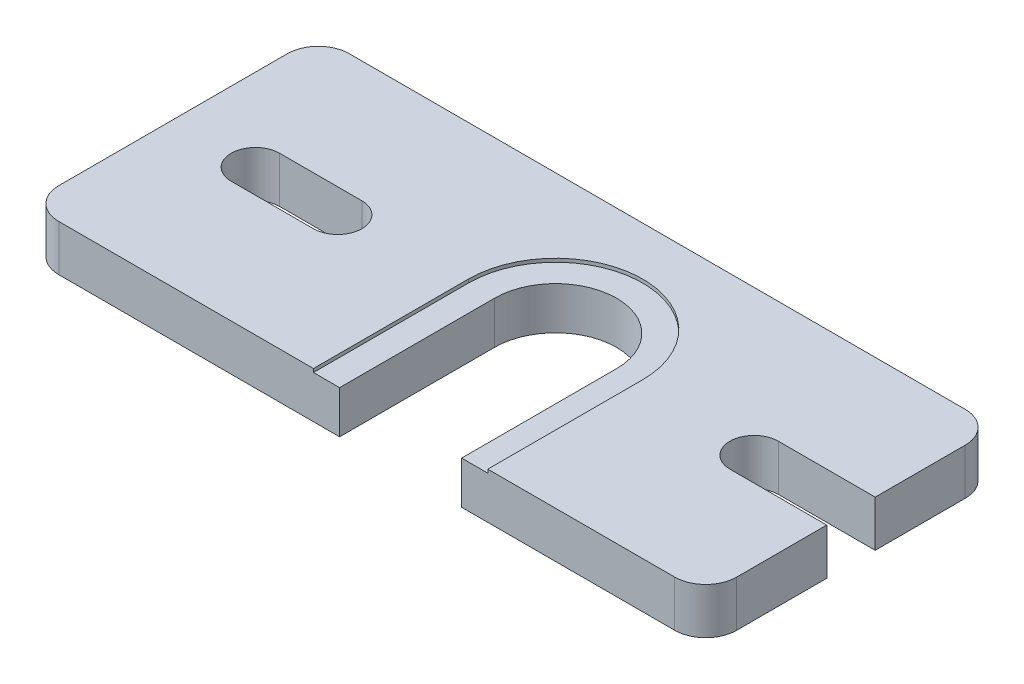
SolidWorks part; units mm, degrees
note: The reader was unsure of these and kept them because the rebuilt part matched: thickness of "Base-Flange1", "Sheet-Metal(1)", "Sheet-Metal(2)", "Sheet-Metal(3)", "Sheet-Metal(6)".
ref_plane "Front Plane" through (0, 0, 0) normal (0, 0, 1) x (1, 0, 0)
ref_plane "Top Plane" through (0, 0, 0) normal (0, 1, 0) x (1, 0, 0)
ref_plane "Right Plane" through (0, 0, 0) normal (1, 0, 0) x (0, 0, -1)
sketch "Sketch2" plane through (0, 0, 0) normal (0, 1, 0) x (1, 0, 0)
  line L0 (-1000, 0) -> (49000, 0) construction
  line L1 (-33.3067, 16.9945) -> (30.2933, 16.9945)
  line L2 (-36.5067, 13.7945) -> (-36.5067, -9.8055)
  line L3 (-33.3067, -13.0055) -> (30.2933, -13.0055)
  line L4 (33.4933, 13.7945) -> (33.4933, -9.8055)
  line L5 (0, -1000) -> (0, 49000) construction
  arc A0 (-33.3067, 16.9945) -> (-36.5067, 13.7945) centre (-33.3067, 13.7945) ccw
  arc A1 (33.4933, 13.7945) -> (30.2933, 16.9945) centre (30.2933, 13.7945) ccw
  arc A2 (-33.3067, -13.0055) -> (-36.5067, -9.8055) centre (-33.3067, -9.8055) cw
  arc A3 (33.4933, -9.8055) -> (30.2933, -13.0055) centre (30.2933, -9.8055) cw
  point P11 (-36.5067, 16.9945)
  point P14 (33.4933, 16.9945)
  point P17 (-36.5067, -13.0055)
  dimension "D3" = 3.2
  dimension "D4" = 3.2
  dimension "D5" = 3.2
  dimension "D6" = 3.2
  dimension "D1" = 70
  dimension "D2" = 30
base flange "Base-Flange1" sketch "Sketch2" thickness 4.4 reverse thickness direction no parameters "D1"=0.7366
sketch "Sketch7" plane through (0, 0, 0) normal (0, 1, 0) x (1, 0, 0)
  line L0 (-28.0067, 1.9945) -> (-19.5067, 1.9945) construction
  line L1 (-28.0067, 4.4945) -> (-19.5067, 4.4945)
  line L2 (-28.0067, -0.5055) -> (-19.5067, -0.5055)
  line L3 (23.4933, 1.9945) -> (33.4933, 1.9945) construction
  line L4 (33.4933, -9.8055) -> (33.4933, 13.7945) construction
  line L5 (23.4933, 4.4945) -> (33.4933, 4.4945)
  line L6 (23.4933, -0.5055) -> (33.4933, -0.5055)
  line L7 (30.2933, 16.9945) -> (-33.3067, 16.9945) construction
  line L8 (-36.5067, 13.7945) -> (-36.5067, -9.8055) construction
  arc A0 (-28.0067, 4.4945) -> (-28.0067, -0.5055) centre (-28.0067, 1.9945) ccw
  arc A1 (-19.5067, -0.5055) -> (-19.5067, 4.4945) centre (-19.5067, 1.9945) ccw
  arc A2 (23.4933, 4.4945) -> (23.4933, -0.5055) centre (23.4933, 1.9945) ccw
  arc A3 (33.4933, -0.5055) -> (33.4933, 4.4945) centre (33.4933, 1.9945) ccw
  point P2 (-23.7567, 1.9945)
  point P7 (28.4933, 1.9945)
  point P20 (-36.5067, 1.7267)
  dimension "D5" = 2.5
  dimension "D6" = 2.5
  dimension "D1" = 15
  dimension "D2" = 8.5
  dimension "D3" = 17
  dimension "D4" = 10
extrude "Cut-Extrude1" cut sketch "Sketch7" against normal blind 4.76 and the other way blind 10.36 contours L2 A1 L1 A0 | L6 A3 L5 A2 normal cut yes
sketch "Sketch8" plane through (0, 0, 0) normal (0, 1, 0) x (1, 0, 0)
  line L0 (1.9933, 2.9945) -> (1.9933, -13.0055) construction
  line L1 (10.9933, 2.9945) -> (10.9933, -13.0055)
  line L2 (-7.0067, 2.9945) -> (-7.0067, -13.0055)
  line L3 (8.2933, 2.9945) -> (8.2933, -13.0055)
  line L4 (-4.3067, 2.9945) -> (-4.3067, -13.0055)
  line L6 (-36.5067, 13.7945) -> (-36.5067, -9.8055) construction
  arc A0 (8.2933, 2.9945) -> (-4.3067, 2.9945) centre (1.9933, 2.9945) ccw
  arc A1 (-4.3067, -13.0055) -> (8.2933, -13.0055) centre (1.9933, -13.0055) ccw
  arc A2 (-7.0067, -13.0055) -> (10.9933, -13.0055) centre (1.9933, -13.0055) ccw
  arc A3 (10.9933, 2.9945) -> (-7.0067, 2.9945) centre (1.9933, 2.9945) ccw
  point P4 (1.9933, -5.0055)
  point P9 (0, 0)
  dimension "D2" = 6.3
  dimension "D4" = 2.7
  dimension "D1" = 16
  dimension "D3" = 38.5
extrude "Cut-Extrude2" cut sketch "Sketch8" against normal blind 4.76 contours A0 L4 A1 L3 normal cut yes
sketch "Sketch11" plane through (0, 0, 0) normal (0, 1, 0) x (1, 0, 0)
  line L0 (-36.5067, 13.7945) -> (-36.5067, -9.8055) construction
  line L1 (30.2933, 16.9945) -> (-33.3067, 16.9945) construction
  line L2 (33.4933, 4.4945) -> (33.4933, 13.7945) construction
  line L3 (23.4933, 4.4945) -> (33.4933, 4.4945) construction
  line L4 (23.4933, -0.5055) -> (33.4933, -0.5055) construction
  line L5 (33.4933, -9.8055) -> (33.4933, -0.5055) construction
  line L6 (8.2933, -13.0055) -> (30.2933, -13.0055) construction
  line L7 (-33.3067, -13.0055) -> (-4.3067, -13.0055) construction
  line L8 (-36.5067, 13.7945) -> (-36.5067, -9.8055)
  line L9 (30.2933, 16.9945) -> (-33.3067, 16.9945)
  line L10 (33.4933, 4.4945) -> (33.4933, 13.7945)
  line L11 (23.4933, 4.4945) -> (33.4933, 4.4945)
  line L12 (23.4933, -0.5055) -> (33.4933, -0.5055)
  line L13 (33.4933, -9.8055) -> (33.4933, -0.5055)
  line L14 (10.9933, -13.0055) -> (30.2933, -13.0055)
  line L15 (-33.3067, -13.0055) -> (-7.0067, -13.0055)
  line L16 (1.9933, 2.9945) -> (1.9933, -13.0055) construction
  line L17 (10.9933, 2.9945) -> (10.9933, -13.0055)
  line L18 (-7.0067, 2.9945) -> (-7.0067, -13.0055)
  line L19 (-19.5067, 4.4945) -> (-28.0067, 4.4945) construction
  line L20 (-19.5067, -0.5055) -> (-28.0067, -0.5055) construction
  line L21 (-19.5067, 4.4945) -> (-28.0067, 4.4945)
  line L22 (-19.5067, -0.5055) -> (-28.0067, -0.5055)
  arc A0 (23.4933, 4.4945) -> (23.4933, -0.5055) centre (23.4933, 1.9945) ccw construction
  arc A1 (30.2933, -13.0055) -> (33.4933, -9.8055) centre (30.2933, -9.8055) ccw construction
  arc A2 (-36.5067, -9.8055) -> (-33.3067, -13.0055) centre (-33.3067, -9.8055) ccw construction
  arc A3 (-33.3067, 16.9945) -> (-36.5067, 13.7945) centre (-33.3067, 13.7945) ccw construction
  arc A4 (33.4933, 13.7945) -> (30.2933, 16.9945) centre (30.2933, 13.7945) ccw construction
  arc A5 (23.4933, 4.4945) -> (23.4933, -0.5055) centre (23.4933, 1.9945) ccw
  arc A6 (30.2933, -13.0055) -> (33.4933, -9.8055) centre (30.2933, -9.8055) ccw
  arc A7 (-36.5067, -9.8055) -> (-33.3067, -13.0055) centre (-33.3067, -9.8055) ccw
  arc A8 (-33.3067, 16.9945) -> (-36.5067, 13.7945) centre (-33.3067, 13.7945) ccw
  arc A9 (33.4933, 13.7945) -> (30.2933, 16.9945) centre (30.2933, 13.7945) ccw
  arc A10 (10.9933, 2.9945) -> (-7.0067, 2.9945) centre (1.9933, 2.9945) ccw
  arc A11 (-19.5067, -0.5055) -> (-19.5067, 4.4945) centre (-19.5067, 1.9945) ccw construction
  arc A12 (-28.0067, 4.4945) -> (-28.0067, -0.5055) centre (-28.0067, 1.9945) ccw construction
  arc A13 (-19.5067, -0.5055) -> (-19.5067, 4.4945) centre (-19.5067, 1.9945) ccw
  arc A14 (-28.0067, 4.4945) -> (-28.0067, -0.5055) centre (-28.0067, 1.9945) ccw
  point P21 (1.9933, -5.0055)
  dimension "D1" = 9
  dimension "D2" = 0
  dimension "D3" = 16
  dimension "D4" = 38.5
extrude "Boss-Extrude1" add sketch "Sketch11" along normal blind 0.36
sketch "Bend-Lines1" plane through (0, 0, 0) normal (0, 1, 0) x (1, 0, 0)
sketch "Bounding-Box1" plane through (0, 0, 0) normal (0, 1, 0) x (1, 0, 0)
sheet metal parameters "Sheet-Metal(1)" thickness 4.4 parameters "D1"=0.7366
flat pattern "Flat-Pattern(1)" [suppressed]
sketch "Bend-Lines2" plane through (0, 0, 0) normal (0, 1, 0) x (1, 0, 0)
sketch "Bounding-Box2" [suppressed] plane through (0, 0, 0) normal (0, 1, 0) x (1, 0, 0)
sheet metal parameters "Sheet-Metal(2)" thickness 4.4 parameters "D1"=0.7366, "D7"=4.76
flat pattern "Flat-Pattern(1)"
sketch "Bend-Lines2" plane through (0, 0, 0) normal (0, 1, 0) x (1, 0, 0)
sketch "Bounding-Box2" [suppressed] plane through (0, 0, 0) normal (0, 1, 0) x (1, 0, 0)
sheet metal parameters "Sheet-Metal(3)" thickness 4.4 parameters "D1"=0.7366, "D7"=4.76
flat pattern "Flat-Pattern(1)"
sketch "Bend-Lines2" plane through (0, 0, 0) normal (0, 1, 0) x (1, 0, 0)
sketch "Bounding-Box2" [suppressed] plane through (0, 0, 0) normal (0, 1, 0) x (1, 0, 0)
sheet metal parameters "Sheet-Metal(6)" thickness 4.4 parameters "D1"=0.7366, "D7"=4.76
flat pattern "Flat-Pattern(1)"
sketch "Bend-Lines2" plane through (0, 0, 0) normal (0, 1, 0) x (1, 0, 0)
sketch "Bounding-Box2" [suppressed] plane through (0, 0, 0) normal (0, 1, 0) x (1, 0, 0)
